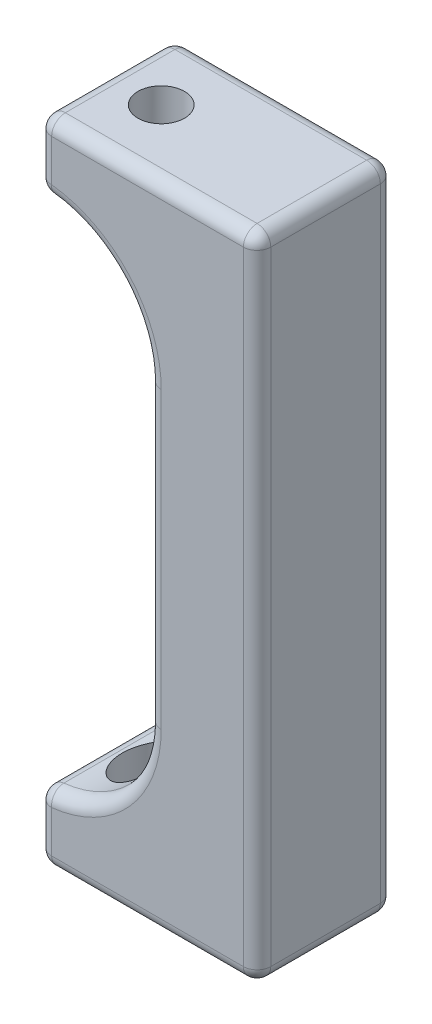
SolidWorks part; units mm, degrees
ref_plane "Front Plane" through (0, 0, 0) normal (0, 0, 1) x (1, 0, 0)
ref_plane "Top Plane" through (0, 0, 0) normal (0, 1, 0) x (1, 0, 0)
ref_plane "Right Plane" through (0, 0, 0) normal (1, 0, 0) x (0, 0, -1)
sketch "Sketch1" plane through (0, 0, 0) normal (0, 0, 1) x (1, 0, 0)
  line L0 (4, 0) -> (-38.3542, 0) construction
  line L1 (-4, -23.75) -> (4, -23.75)
  line L2 (-4, -23.75) -> (-4, 23.75)
  line L3 (-4, 23.75) -> (4, 23.75)
  line L4 (4, -23.75) -> (4, 23.75)
  line L5 (-4, -23.75) -> (4, 23.75) construction
  line L6 (-4, 23.75) -> (4, -23.75) construction
  line L7 (-4, 23.75) -> (-12, 23.75)
  line L8 (-4, 23.75) -> (-4, 18.75)
  line L9 (-4, 18.75) -> (-12, 18.75)
  line L10 (-12, 23.75) -> (-12, 18.75)
  line L11 (-4, -18.75) -> (-12, -18.75)
  line L12 (-12, -23.75) -> (-12, -18.75)
  line L13 (-4, -23.75) -> (-12, -23.75)
  line L14 (-4, -23.75) -> (-4, -18.75)
  point P0 (0, 0)
  dimension "D1" = 8
  dimension "D2" = 47.5
  dimension "D3" = 5
  dimension "D4" = 8
extrude "Boss-Extrude1" add sketch "Sketch1" along normal blind 10 contours L7 L10 L9 L2 | L1 L4 L3 L2 | L13 L2 L11 L12 region at (0, 0, 0) region at (-8, -21.25, 0) region at (-8, 21.25, 0)
sketch "Sketch2" plane through (0, 23.75, 0) normal (0, 1, 0) x (1, 0, 0)
  line L0 (-12, -5) -> (-4, -5) construction
  line L1 (-8, 0) -> (-8, -10) construction
  line L4 (-4, 0) -> (-12, 0)
  line L5 (-12, 0) -> (-12, -10)
  line L6 (-12, -10) -> (-4, -10)
  line L7 (-4, -10) -> (-4, 0)
  line L8 (-4, 0) -> (-12, 0)
  line L9 (-12, 0) -> (-12, -10)
  line L10 (-12, -10) -> (-4, -10)
  line L11 (-4, -10) -> (-4, 0)
  circle A0 centre (-8, -5) radius 1.7
  dimension "D2" = 3.4
  dimension "D1" = 0
extrude "Cut-Extrude1" cut sketch "Sketch2" against normal through all contours A0 region at (-8, 23.75, 5)
sketch "Sketch3" plane through (0, -18.75, 0) normal (0, 1, 0) x (1, 0, 0)
  circle A0 centre (-8, -5) radius 2.85
  dimension "D1" = 5.7
extrude "Cut-Extrude2" cut sketch "Sketch3" against normal blind 2.5 and the other way blind 40
fillet "Fillet1" radius 8 2 edges at (-4, 18.75, 5) (-4, -18.75, 5)
fillet "Fillet2" radius 1 22 edges at (-12, 23.75, 5) (-12, 18.75, 5) (-12, -18.75, 5) (-12, -23.75, 5) (-12, 21.25, 0) (-6.3431, 16.4069, 0) (-4, 0, 0) (-6.3431, -16.4069, 0) (-12, -21.25, 0) (-4, -23.75, 0) (-4, 23.75, 0) (4, -23.75, 5) (4, 23.75, 5) (4, 0, 0) (4, 0, 10) (-4, -23.75, 10) (-12, -21.25, 10) (-6.3431, -16.4069, 10) (-4, 0, 10) (-6.3431, 16.4069, 10) (-12, 21.25, 10) (-4, 23.75, 10)
